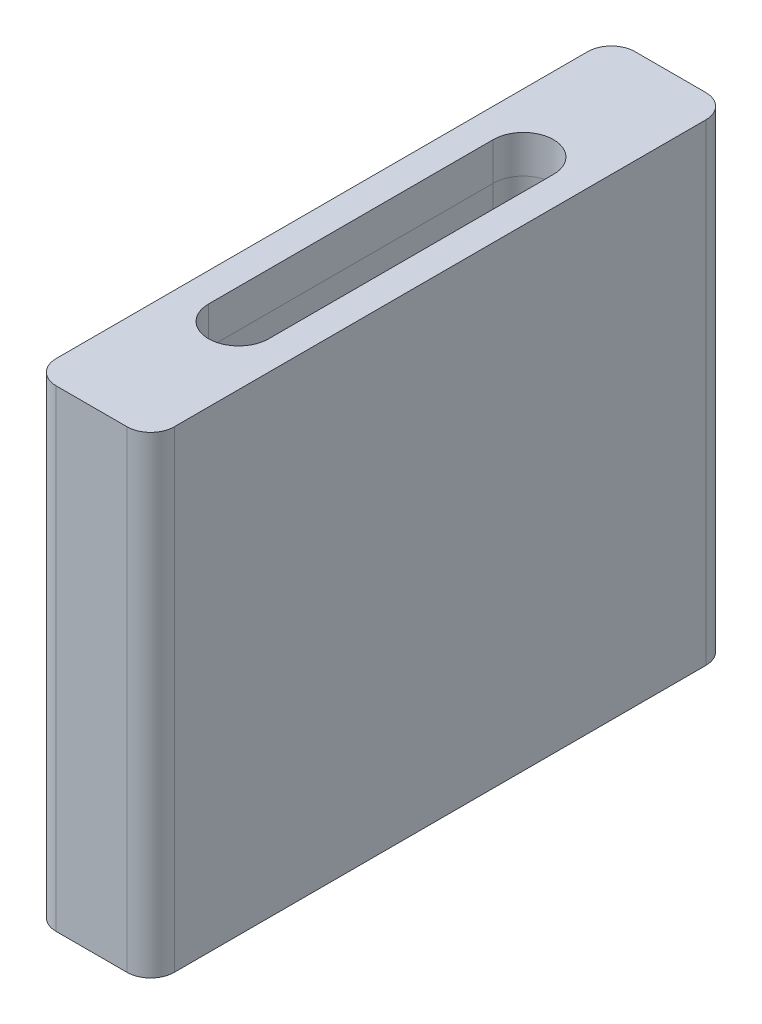
SolidWorks part; units mm, degrees
material "K110"
ref_plane "Front Plane" through (0, 0, 0) normal (0, 0, 1) x (1, 0, 0)
ref_plane "Top Plane" through (0, 0, 0) normal (0, 1, 0) x (1, 0, 0)
ref_plane "Right Plane" through (0, 0, 0) normal (1, 0, 0) x (0, 0, -1)
sketch "Sketch1" plane through (0, 0, 0) normal (0, 1, 0) x (1, 0, 0)
  line L3 (0, -3.5) -> (0, 3.5) construction
  line L4 (-2.62, -3.5) -> (-2.62, 3.5) construction
  line L5 (2.62, -3.5) -> (2.62, 3.5) construction
  line L6 (-3, -24.5) -> (3, -24.5)
  line L7 (-5, -22.5) -> (-5, 22.5)
  line L8 (-3, 24.5) -> (3, 24.5)
  line L9 (5, -22.5) -> (5, 22.5)
  line L10 (-5, -24.5) -> (5, 24.5) construction
  line L11 (-5, 24.5) -> (5, -24.5) construction
  arc A2 (-2.62, -3.5) -> (2.62, -3.5) centre (0, -3.5) ccw construction
  arc A3 (2.62, 3.5) -> (-2.62, 3.5) centre (0, 3.5) ccw construction
  arc A4 (-3, -24.5) -> (-5, -22.5) centre (-3, -22.5) cw
  arc A5 (3, -24.5) -> (5, -22.5) centre (3, -22.5) ccw
  arc A6 (3, 24.5) -> (5, 22.5) centre (3, 22.5) cw
  arc A7 (-5, 22.5) -> (-3, 24.5) centre (-3, 22.5) cw
  point P0 (0, 0)
  point P10 (0, 0)
  dimension "D1" = 7
  dimension "D3" = 2.62
  dimension "D5" = 2
  dimension "D2" = 49
  dimension "D4" = 10
extrude "Boss-Extrude1" add sketch "Sketch1" against normal blind 40
sketch "Sketch5" plane through (0, 0, 0) normal (0, 1, 0) x (1, 0, 0)
  line L0 (0, -12.05) -> (0, 12.05) construction
  line L1 (-2.55, -12.05) -> (-2.55, 12.05)
  line L2 (2.55, -12.05) -> (2.55, 12.05)
  arc A0 (-2.55, -12.05) -> (2.55, -12.05) centre (0, -12.05) ccw
  arc A1 (2.55, 12.05) -> (-2.55, 12.05) centre (0, 12.05) ccw
  point P2 (0, 0)
  point P3 (0, 2.2945)
  point P4 (0, 0)
  point P9 (0, 0)
  point P10 (0, -8.5)
  point P11 (0, 0)
  dimension "D1" = 24.1
  dimension "D2" = 5.1
extrude "Cut-Extrude2" cut sketch "Sketch5" against normal up to next
sketch "Sketch7" plane through (0, 0, 0) normal (0, 0, 1) x (1, 0, 0)
  line L0 (2.55, -3.2) -> (3.1923, -40)
  line L1 (2.55, -40) -> (2.55, 0) construction
  line L2 (-3, -40) -> (3, -40) construction
  line L3 (3.1923, -40) -> (2.55, -40)
  line L4 (2.55, -40) -> (2.55, -3.2)
  line L5 (5, 0) -> (3, 0) construction
  dimension "D1" = 3.2
  dimension "D2" = 1
sketch "Sketch8" plane through (0, 0, 0) normal (0, 1, 0) x (1, 0, 0)
  line L0 (-2.55, 12.05) -> (-2.55, -12.05) construction
  line L1 (2.55, -12.05) -> (2.55, 12.05) construction
  line L2 (-2.55, 12.05) -> (-2.55, -12.05)
  line L3 (2.55, -12.05) -> (2.55, 12.05)
  arc A0 (2.55, 12.05) -> (-2.55, 12.05) centre (0, 12.05) ccw construction
  arc A1 (-2.55, -12.05) -> (2.55, -12.05) centre (0, -12.05) ccw construction
  arc A2 (2.55, 12.05) -> (-2.55, 12.05) centre (0, 12.05) ccw
  arc A3 (-2.55, -12.05) -> (2.55, -12.05) centre (0, -12.05) ccw
sweep "Cut-Sweep1" cut profiles "Sketch7" path "Sketch8"
hole_wizard "M6 Tapped Hole1" positions "Sketch11" profile "Sketch10" tap size "M6" standard "ISO"
sketch "Sketch11" plane through (0, -40, 0) normal (0, -1, 0) x (-1, 0, 0)
  line L0 (-3, 24.5) -> (3, 24.5) construction
  line L5 (3, -24.5) -> (-3, -24.5) construction
  line L6 (0, 24.5) -> (0, -24.5) construction
  point P0 (0, 19.5)
  point P2 (0, -19.5)
  point P31 (0, 0)
  point P32 (0, 0)
  dimension "D1" = 5
  dimension "D4" = 5
sketch "Sketch10" plane through (0, -40, -19.5) normal (1, 0, 0) x (0, 0, -1)
  line L0 (0, 0) -> (0, 18.5022)
  line L1 (0, 18.5022) -> (2.5, 17)
  line L2 (2.5, 17) -> (2.5, 0.525)
  line L3 (2.5, 0.525) -> (3.025, 0)
  line L5 (3.025, 0) -> (0, 0)
  line L6 (-2.5, 0.525) -> (-3.025, 0) construction
  line L10 (0, 18.5022) -> (-2.5, 17) construction
  line L11 (0, -6.35) -> (0, 107.95) construction
  dimension "Tap Drill Dia." = 5
  dimension "Tap Drill Depth" = 17
  dimension "Near C'Sink Dia." = 6.05
  dimension "Near C'Sink Angle" = 90
  dimension "Drill Angle" = 118
cosmetic thread "Hole Thread1"
cosmetic thread "Hole Thread2"
